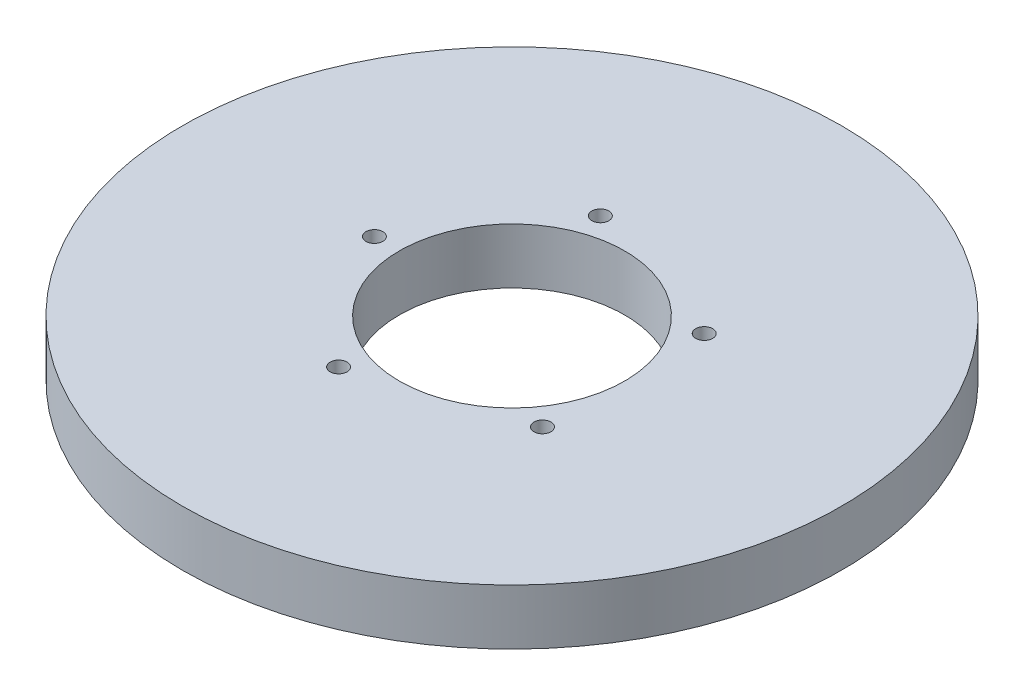
SolidWorks part; units mm, degrees
ref_plane "Front Plane" through (0, 0, 0) normal (0, 0, 1) x (1, 0, 0)
ref_plane "Top Plane" through (0, 0, 0) normal (0, 1, 0) x (1, 0, 0)
ref_plane "Right Plane" through (0, 0, 0) normal (1, 0, 0) x (0, 0, -1)
sketch "Sketch1" plane through (0, 0, 0) normal (0, 1, 0) x (1, 0, 0)
  circle A0 centre (0, 0) radius 95
  dimension "FLANGE_OD" = 190
extrude "Boss-Extrude1" add sketch "Sketch1" along normal blind 16
sketch "Sketch2" plane through (0, 0, 0) normal (0, 1, 0) x (1, 0, 0)
  circle A0 centre (0, 0) radius 32.5
  dimension "BORE_D" = 65
extrude "Cut-Extrude1" cut sketch "Sketch2" along normal through all
sketch "Sketch3" plane through (0, 16, 0) normal (0, 1, 0) x (1, 0, 0)
  circle A0 centre (0, 0) radius 39.6623 construction
  circle A1 centre (-39.6623, 0) radius 2.4447
  dimension "BOLT_D" = 4.8895
  dimension "BOLT_PCD" = 79.3245
extrude "Cut-Extrude2" cut sketch "Sketch3" against normal blind 10.6627
pattern_circular "CirPattern1" count 5 over 360 about axis through (0, 0, 0) along (0, 1, 0) of "Cut-Extrude2"
